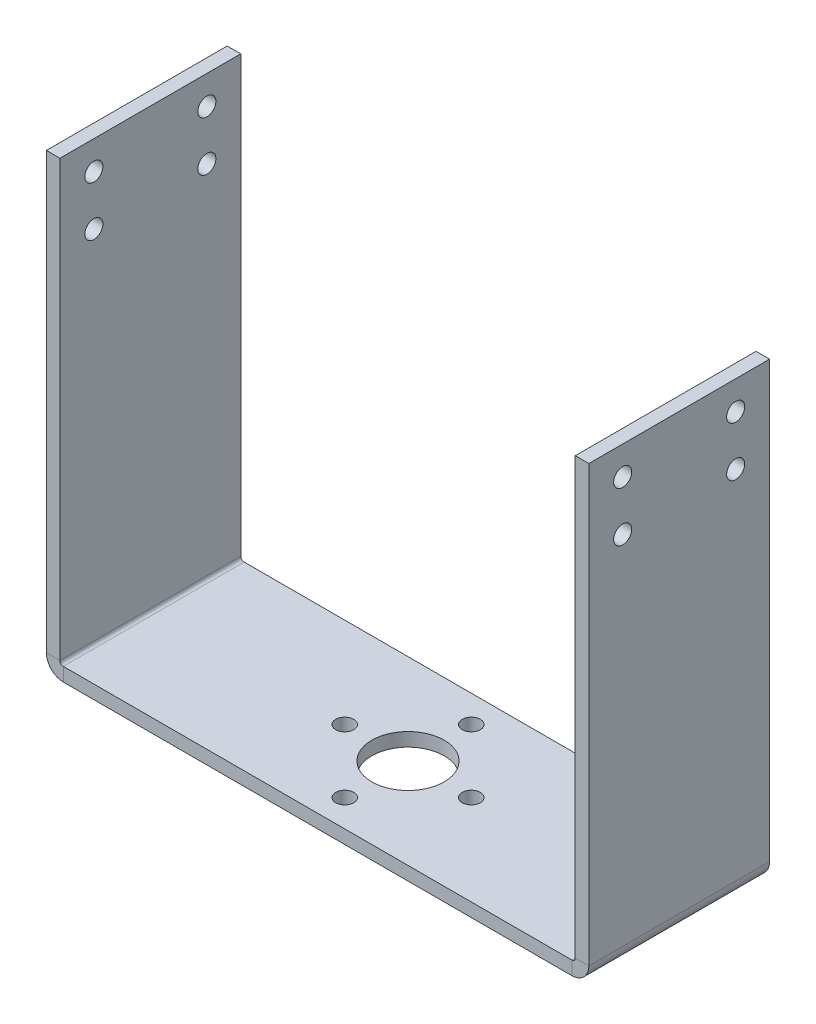
SolidWorks part; units mm, degrees
note: The reader was unsure of these and kept them because the rebuilt part matched: flange length of "Edge-Flange1", "Edge-Flange2".
material "Alloy Steel (SS)"
ref_plane "Front Plane" through (0, 0, 0) normal (0, 0, 1) x (1, 0, 0)
ref_plane "Top Plane" through (0, 0, 0) normal (0, 1, 0) x (1, 0, 0)
ref_plane "Right Plane" through (0, 0, 0) normal (1, 0, 0) x (0, 0, -1)
sketch "Sketch3" plane through (0, 0, 0) normal (0, 1, 0) x (1, 0, 0)
  line L6 (-57, 20) -> (57, 20)
  line L18 (-57, 20) -> (-57, -20)
  line L19 (-57, -20) -> (57, -20)
  line L20 (57, 20) -> (57, -20)
  line L21 (-57, 20) -> (57, -20) construction
  line L22 (-57, -20) -> (57, 20) construction
  point P0 (0, 0)
  dimension "D1" = 40
  dimension "D2" = 114
base flange "Base-Flange1" sketch "Sketch3" thickness 3 reverse thickness direction no parameters "D1"=0.7366
edge flange "Edge-Flange1" sketch "Sketch7" flange angle 90 flange length 100 flange position material outside bend radius 0.7366 thickness 3 relief rectangular parameters "D6"=10
sketch "Sketch7" plane through (-57, 0, 0) normal (-1, 0, 0) x (0, 0, 1)
  line L0 (-20, 0) -> (20, 0) construction
  line L1 (-20, 0) -> (20, 0)
  line L2 (-20, 0) -> (-20, 97)
  line L3 (-20, 97) -> (20, 97)
  line L4 (20, 97) -> (20, 0)
bend "EdgeBend1" bend radius 0.7366 bend angle 90 parameters "D5"=1
edge flange "Edge-Flange2" sketch "Sketch10" flange angle 90 flange length 100 flange position material outside bend radius 0.7366 thickness 3 relief rectangular parameters "D6"=10
sketch "Sketch10" plane through (57, 0, 0) normal (1, 0, 0) x (0, 0, -1)
  line L0 (-20, 0) -> (20, 0) construction
  line L1 (-20, 0) -> (20, 0)
  line L2 (-20, 0) -> (-20, 97)
  line L3 (-20, 97) -> (20, 97)
  line L4 (20, 97) -> (20, 0)
bend "EdgeBend2" bend radius 0.7366 bend angle 90 parameters "D5"=2
sketch "Sketch11" plane through (0, -3, 0) normal (0, -1, 0) x (-1, 0, 0)
  line L0 (-56.2634, 20) -> (56.2634, -20) construction
  line L1 (56.2634, 20) -> (-56.2634, -20) construction
  line L2 (0, 20) -> (0, 8) construction
  line L3 (-56.2634, 20) -> (56.2634, 20) construction
  circle A0 centre (0, 0) radius 8
  circle A1 centre (0, 14) radius 2
  circle A2 centre (14, 0) radius 2
  circle A3 centre (0, -14) radius 2
  circle A4 centre (-14, 0) radius 2
  point P19 (-15.2895, -16.7707)
  point P20 (0, 14)
  point P21 (0, 0)
  point P29 (0, 0)
  dimension "D1" = 16
  dimension "D2" = 4
  dimension "D3" = 4
extrude "Cut-Extrude1" cut sketch "Sketch11" against normal blind 10 normal cut yes
sketch "Sketch12" plane through (60, 0, 0) normal (1, 0, 0) x (0, 0, -1)
  circle A0 centre (12.5, 79.6742) radius 2
  circle A1 centre (12.5, 90.6742) radius 2
  circle A2 centre (-12.5, 79.6742) radius 2
  circle A3 centre (-12.5, 90.6742) radius 2
  dimension "D1" = 4
  dimension "D2" = 4
  dimension "D3" = 4
  dimension "D4" = 4
extrude "Cut-Extrude2" cut sketch "Sketch12" against normal up to surface (120 mm away) normal cut yes up to face at (-60, 48.8683, 0)
sketch "Sketch14" plane through (60, 0, 0) normal (1, 0, 0) x (0, 0, -1)
  line L0 (-12.5, 64.5) -> (12.5, 8.2366) construction
  line L6 (-12.5, 8.2366) -> (12.5, 64.5) construction
  line L7 (-12.5, 72) -> (-12.5, 64.5) construction
  line L32 (-17, 72) -> (-8, 72) construction
  line L33 (-12.5, 64.5) -> (-20, 64.5) construction
  line L34 (-20, 97) -> (-20, 0.7366) construction
  line L35 (12.5, 72) -> (12.5, 64.5) construction
  line L36 (8, 72) -> (17, 72) construction
  line L37 (12.5, 64.5) -> (20, 64.5) construction
  line L38 (20, 0.7366) -> (20, 97) construction
  line L39 (12.5, 0.7366) -> (12.5, 8.2366) construction
  line L40 (20, 0.7366) -> (-20, 0.7366) construction
  line L41 (12.5, 8.2366) -> (20, 8.2366) construction
  line L42 (-12.5, 0.7366) -> (-12.5, 8.2366) construction
  line L43 (-12.5, 8.2366) -> (-20, 8.2366) construction
  point P22 (0, 0)
  point P24 (0, 0)
  point P25 (-12.5, 72)
  point P26 (12.5, 72)
  point P27 (-10.6778, 17.2759)
  point P28 (-12.5, 64.5)
sketch "Sketch15" plane through (60, 0, 0) normal (1, 0, 0) x (0, 0, -1)
  line L0 (-12.5, 58.9024) -> (-12.5, 13.8342)
  line L1 (-12.5, 13.8342) -> (-2.4872, 36.3683)
  line L2 (-2.4872, 36.3683) -> (-12.5, 58.9024)
  line L3 (12.5, 58.9024) -> (2.4872, 36.3683)
  line L4 (2.4872, 36.3683) -> (12.5, 13.8342)
  line L5 (12.5, 13.8342) -> (12.5, 58.9024)
  line L6 (-9.7116, 64.5) -> (0, 42.6436)
  line L7 (0, 42.6436) -> (9.7116, 64.5)
  line L8 (9.7116, 64.5) -> (-9.7116, 64.5)
  line L9 (-9.7116, 8.2366) -> (0, 30.093)
  line L10 (0, 30.093) -> (9.7116, 8.2366)
  line L11 (9.7116, 8.2366) -> (-9.7116, 8.2366)
  line L12 (12.5, 8.2366) -> (20, 8.2366) construction
  line L13 (12.5, 64.5) -> (20, 64.5) construction
  line L14 (12.5, 0.7366) -> (12.5, 8.2366) construction
  line L15 (-12.5, 0.7366) -> (-12.5, 8.2366) construction
  line L16 (-12.5, 8.2366) -> (12.5, 64.5) construction
  line L17 (0, 30.093) -> (0, 36.3683) construction
  line L18 (-12.5, 64.5) -> (12.5, 8.2366) construction
  line L19 (0, 36.3683) -> (0, 42.6436) construction
  line L20 (2.4872, 36.3683) -> (0, 36.3683) construction
  line L21 (0, 36.3683) -> (-2.4872, 36.3683) construction
  point P14 (1.3672, 52.2867)
  point P19 (0, 27.3937)
  point P20 (3.1338, 36.3683)
  point P25 (0, 41.8964)
  point P26 (-2.4872, 36.3683)
  point P29 (0, 30.093)
sketch "Bend-Lines1" [suppressed] plane through (0, 0, 0) normal (0, 1, 0) x (1, 0, 0)
sketch "Bounding-Box1" [suppressed] plane through (0, 0, 0) normal (0, 1, 0) x (1, 0, 0)
sheet metal parameters "Sheet-Metal1" thickness 3 parameters "D1"=0.7366
flat pattern "Flat-Pattern1" [suppressed]
sketch "Bend-Lines2" plane through (0, 0, 0) normal (0, 1, 0) x (1, 0, 0)
sketch3d "Bounding-Box2" [suppressed]
  line L0 (57, -20, 0) -> (-57, -20, 0) construction
  line L1 (57, 20, 0) -> (-57, 20, 0) construction
  line L2 (57, -20, 0) -> (57, 20, 0) construction
  line L3 (-57, -20, 0) -> (-57, 20, 0) construction
sheet metal parameters "Sheet-Metal2" thickness 3 parameters "D1"=0.7366
flat pattern "Flat-Pattern1"
sketch "Bend-Lines2" plane through (0, 0, 0) normal (0, 1, 0) x (1, 0, 0)
  line L0 (-58.02, 20) -> (-58.02, -20) construction
  line L1 (-58.02, 20) -> (-58.02, -20) construction
sketch3d "Bounding-Box2" [suppressed]
  line L0 (57, -20, 0) -> (-90.7766, -20, 0) construction
  line L1 (57, 20, 0) -> (-90.7766, 20, 0) construction
  line L2 (57, -20, 0) -> (57, 20, 0) construction
  line L3 (-90.7766, -20, 0) -> (-90.7766, 20, 0) construction
bend of the flat pattern "Flatten-<EdgeBend1>1"
sheet metal parameters "Sheet-Metal3" thickness 3 parameters "D1"=0.7366
flat pattern "Flat-Pattern1"
sketch "Bend-Lines2" plane through (0, 0, 0) normal (0, 1, 0) x (1, 0, 0)
  line L0 (-58.02, 20) -> (-58.02, -20) construction
  line L1 (-58.02, 20) -> (-58.02, -20) construction
  line L2 (58.02, -20) -> (58.02, 20) construction
  line L3 (58.02, -20) -> (58.02, 20) construction
sketch3d "Bounding-Box2" [suppressed]
  line L0 (156.04, -20, 0) -> (-156.04, -20, 0) construction
  line L1 (156.04, 20, 0) -> (-156.04, 20, 0) construction
  line L2 (156.04, -20, 0) -> (156.04, 20, 0) construction
  line L3 (-156.04, -20, 0) -> (-156.04, 20, 0) construction
bend of the flat pattern "Flatten-<EdgeBend1>1"
bend of the flat pattern "Flatten-<EdgeBend2>1"
sheet metal parameters "Sheet-Metal4" thickness 3 parameters "D1"=0.7366
flat pattern "Flat-Pattern1"
sketch "Bend-Lines2" plane through (0, 0, 0) normal (0, 1, 0) x (1, 0, 0)
  line L0 (-58.02, 20) -> (-58.02, -20) construction
  line L1 (-58.02, 20) -> (-58.02, -20) construction
  line L2 (58.02, -20) -> (58.02, 20) construction
  line L3 (58.02, -20) -> (58.02, 20) construction
sketch3d "Bounding-Box2" [suppressed]
  line L0 (156.04, -20, 0) -> (-156.04, -20, 0) construction
  line L1 (156.04, 20, 0) -> (-156.04, 20, 0) construction
  line L2 (156.04, -20, 0) -> (156.04, 20, 0) construction
  line L3 (-156.04, -20, 0) -> (-156.04, 20, 0) construction
bend of the flat pattern "Flatten-<EdgeBend1>1"
bend of the flat pattern "Flatten-<EdgeBend2>1"
sheet metal parameters "Sheet-Metal5" thickness 3 parameters "D1"=0.7366
flat pattern "Flat-Pattern1"
sketch "Bend-Lines2" plane through (0, 0, 0) normal (0, 1, 0) x (1, 0, 0)
  line L0 (-58.02, 20) -> (-58.02, -20) construction
  line L1 (-58.02, 20) -> (-58.02, -20) construction
  line L2 (58.02, -20) -> (58.02, 20) construction
  line L3 (58.02, -20) -> (58.02, 20) construction
sketch3d "Bounding-Box2" [suppressed]
  line L0 (156.04, -20, 0) -> (-156.04, -20, 0) construction
  line L1 (156.04, 20, 0) -> (-156.04, 20, 0) construction
  line L2 (156.04, -20, 0) -> (156.04, 20, 0) construction
  line L3 (-156.04, -20, 0) -> (-156.04, 20, 0) construction
bend of the flat pattern "Flatten-<EdgeBend1>1"
bend of the flat pattern "Flatten-<EdgeBend2>1"
